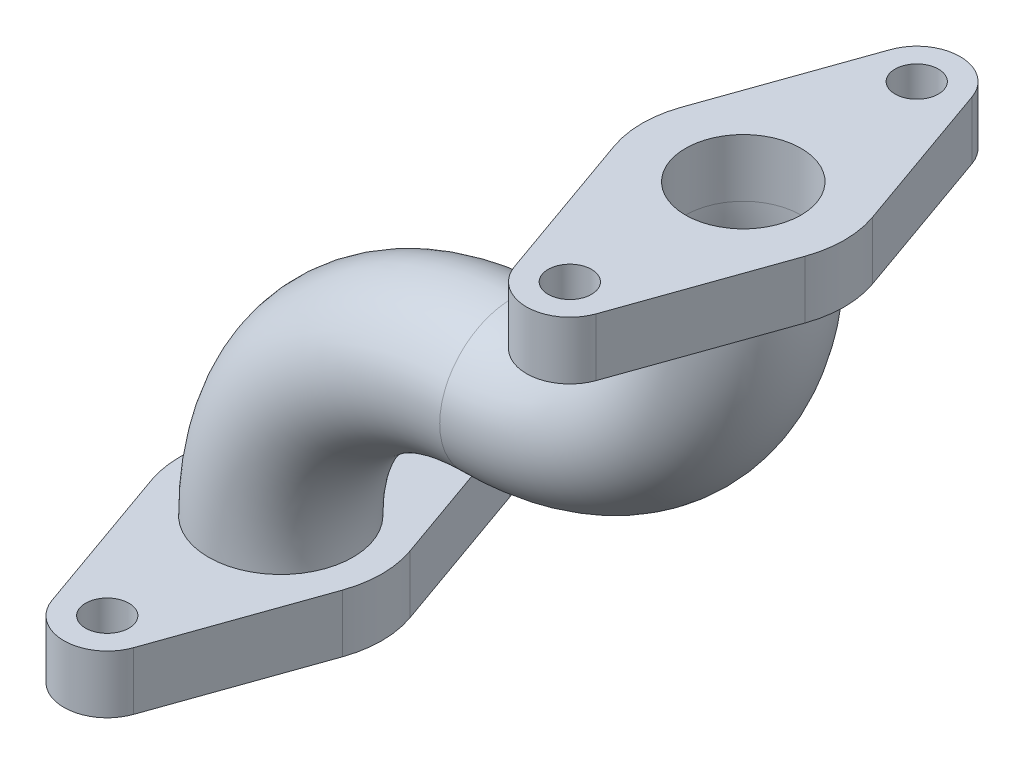
SolidWorks part; units mm, degrees
material "PVC Rigid"
ref_plane "Front Plane" through (0, 0, 0) normal (0, 0, 1) x (1, 0, 0)
ref_plane "Top Plane" through (0, 0, 0) normal (0, 1, 0) x (1, 0, 0)
ref_plane "Right Plane" through (0, 0, 0) normal (1, 0, 0) x (0, 0, -1)
sketch "Sketch1" plane through (0, 0, 0) normal (0, 1, 0) x (1, 0, 0)
  line L0 (0, 0) -> (0, 38.1) construction
  line L1 (0, 38.1) -> (0, -38.1) construction
  line L2 (8.9803, -41.275) -> (20.9539, -7.4083)
  line L3 (20.9539, 7.4083) -> (8.9803, 41.275)
  line L4 (-8.9803, -41.275) -> (-20.9539, -7.4083)
  line L5 (-20.9539, 7.4083) -> (-8.9803, 41.275)
  circle A0 centre (0, 0) radius 15.875
  circle A1 centre (0, 0) radius 12.7
  circle A2 centre (0, 38.1) radius 4.7625
  circle A3 centre (0, -38.1) radius 4.7625
  arc A4 (-8.9803, -41.275) -> (8.9803, -41.275) centre (0, -38.1) ccw
  arc A5 (8.9803, 41.275) -> (-8.9803, 41.275) centre (0, 38.1) ccw
  arc A6 (20.9539, -7.4083) -> (20.9539, 7.4083) centre (0, 0) ccw
  arc A7 (-20.9539, 7.4083) -> (-20.9539, -7.4083) centre (0, 0) ccw
  dimension "D1" = 31.75
  dimension "D2" = 25.4
  dimension "D3" = 9.525
  dimension "D5" = 9.525
  dimension "D7" = 44.45
  dimension "D8" = 19.05
  dimension "D9" = 19.05
  dimension "D4" = 38.1
  dimension "D6" = 38.1
extrude "Boss-Extrude1" add sketch "Sketch1" against normal blind 12.7 contours L5 A7 L4 A4 L2 A6 L3 A5 A0 A2 A3 | A0 A1 region at (0, 0, 46.5739) region at (-15.426, 0, 0)
ref_plane "Plane1" through (0, 101.6, 0) normal (0, 1, 0) x (1, 0, 0)
sketch "Sketch2" plane through (0, 101.6, 0) normal (0, 1, 0) x (1, 0, 0)
  line L0 (0, 0) -> (101.6, 0) construction
  line L1 (101.6, 0) -> (101.6, 38.1) construction
  line L2 (101.6, 38.1) -> (101.6, -38.1) construction
  line L3 (110.5803, -41.275) -> (122.5539, -7.4083)
  line L4 (122.5539, 7.4083) -> (110.5803, 41.275)
  line L5 (92.6197, -41.275) -> (80.6461, -7.4083)
  line L6 (80.6461, 7.4083) -> (92.6197, 41.275)
  circle A0 centre (101.6, 0) radius 15.875
  circle A1 centre (101.6, 0) radius 12.7
  circle A2 centre (101.6, 38.1) radius 4.7625
  circle A3 centre (101.6, -38.1) radius 4.7625
  arc A4 (92.6197, -41.275) -> (110.5803, -41.275) centre (101.6, -38.1) ccw
  arc A5 (110.5803, 41.275) -> (92.6197, 41.275) centre (101.6, 38.1) ccw
  arc A6 (122.5539, -7.4083) -> (122.5539, 7.4083) centre (101.6, 0) ccw
  arc A7 (80.6461, 7.4083) -> (80.6461, -7.4083) centre (101.6, 0) ccw
  point P0 (0, 0)
  point P19 (0, 0)
  point P20 (0, 0)
  dimension "D2" = 9.525
  dimension "D3" = 25.4
  dimension "D4" = 31.75
  dimension "D5" = 22.225
  dimension "D7" = 9.525
  dimension "D8" = 9.525
  dimension "D9" = 38.1
  dimension "D10" = 9.525
  dimension "D1" = 101.6
  dimension "D6" = 33.8667
extrude "Boss-Extrude2" add sketch "Sketch2" along normal blind 12.7 separate body contours L6 A7 L5 A4 L3 A6 L4 A5 A0 A2 A3 | A0 A1 region at (101.6, 101.6, 46.5739) region at (86.174, 101.6, 0)
sketch "Sketch3" plane through (0, 0, 0) normal (0, 0, 1) x (1, 0, 0)
  line L0 (15.875, 0) -> (-15.875, 0) construction
  line L1 (15.875, 0) -> (-15.875, 0)
  arc A0 (0, 0) -> (50.8, 50.8) centre (50.8, 0) cw
  point P5 (50.8, 50.8)
  dimension "D1" = 50.8
  dimension "D2" = 50.8
  dimension "D3" = 50.8
sweep "Sweep-Thin1" add path "Sketch3" circular profile diameter 31.75 parameters "D1"=3.175, "D3"=31.75
sketch "Sketch25" plane through (0, 0, 0) normal (0, 0, 1) x (1, 0, 0)
  line L0 (50.8, 34.925) -> (50.8, 66.675) construction
  line L1 (50.8, 34.925) -> (50.8, 66.675)
  line L2 (92.6197, 101.6) -> (110.5803, 101.6) construction
  line L4 (117.475, 101.6) -> (85.725, 101.6) construction
  line L5 (114.3, 101.6) -> (88.9, 101.6) construction
  line L6 (117.475, 101.6) -> (85.725, 101.6)
  line L7 (114.3, 101.6) -> (88.9, 101.6)
  arc A0 (101.6, 101.6) -> (50.8, 50.8) centre (50.8, 101.6) cw
  dimension "D1" = 50.8
sweep "Sweep-Thin2" add path "Sketch25" circular profile diameter 31.75 parameters "D1"=3.175, "D3"=31.75
